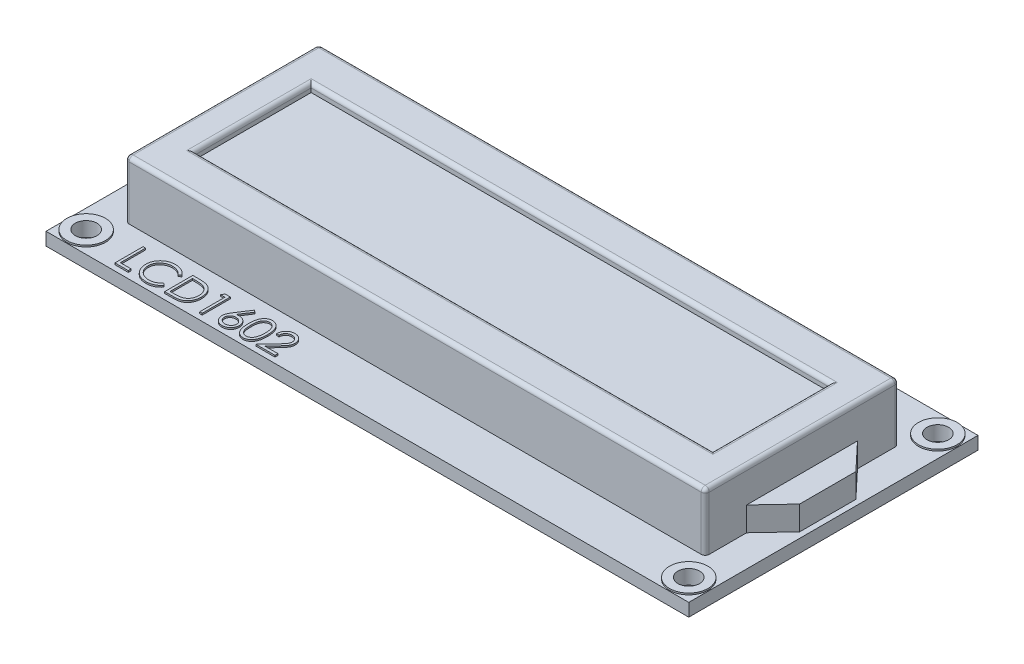
SolidWorks part; units mm, degrees
ref_plane "Front Plane" through (0, 0, 0) normal (0, 0, 1) x (1, 0, 0)
ref_plane "Top Plane" through (0, 0, 0) normal (0, 1, 0) x (1, 0, 0)
ref_plane "Right Plane" through (0, 0, 0) normal (1, 0, 0) x (0, 0, -1)
sketch "Sketch1" plane through (0, 0, 0) normal (0, 1, 0) x (1, 0, 0)
  line L0 (-31.9, 15.9) -> (6.2, 15.9) construction
  line L1 (40, 18) -> (-40, 18)
  line L2 (40, 18) -> (40, -18)
  line L3 (40, -18) -> (-40, -18)
  line L4 (-40, 18) -> (-40, -18)
  line L5 (0, -18) -> (0, 18) construction
  line L6 (40, 0) -> (-40, 0) construction
  line L7 (37.5, -15.5) -> (-37.5, -15.5) construction
  line L8 (37.5, -15.5) -> (37.5, 15.5) construction
  line L9 (37.5, 15.5) -> (-37.5, 15.5) construction
  line L10 (-37.5, -15.5) -> (-37.5, 15.5) construction
  line L11 (0, 15.5) -> (0, -15.5) construction
  line L12 (37.5, 0) -> (-37.5, 0) construction
  circle A0 centre (-37.5, 15.5) radius 1.35
  circle A1 centre (37.5, 15.5) radius 1.35
  circle A2 centre (37.5, -15.5) radius 1.35
  circle A3 centre (-37.5, -15.5) radius 1.35
  circle A4 centre (-31.9, 15.9) radius 0.5
  circle A5 centre (-29.36, 15.9) radius 0.5
  circle A6 centre (-26.82, 15.9) radius 0.5
  circle A7 centre (-24.28, 15.9) radius 0.5
  circle A8 centre (-21.74, 15.9) radius 0.5
  circle A9 centre (-19.2, 15.9) radius 0.5
  circle A10 centre (-16.66, 15.9) radius 0.5
  circle A11 centre (-14.12, 15.9) radius 0.5
  circle A12 centre (-11.58, 15.9) radius 0.5
  circle A13 centre (-9.04, 15.9) radius 0.5
  circle A14 centre (-6.5, 15.9) radius 0.5
  circle A15 centre (-3.96, 15.9) radius 0.5
  circle A16 centre (-1.42, 15.9) radius 0.5
  circle A17 centre (1.12, 15.9) radius 0.5
  circle A18 centre (3.66, 15.9) radius 0.5
  circle A19 centre (6.2, 15.9) radius 0.5
  point P0 (0, 0)
  point P4 (0, 0)
  dimension "D5" = 2
  dimension "D10" = 1
  dimension "D11" = 16
  dimension "D1" = 80
  dimension "D2" = 36
  dimension "D3" = 31
  dimension "D4" = 75
  dimension "D7" = 8.1
  dimension "D8" = 2.1
  dimension "D9" = 38.1
  dimension "D6" = 2
extrude "Boss-Extrude1" add sketch "Sketch1" along normal blind 1.6
sketch "Sketch2" plane through (0, 1.6, 0) normal (0, 1, 0) x (1, 0, 0)
  line L1 (36.1, 12.05) -> (-36.1, 12.05)
  line L2 (36.1, 12.05) -> (36.1, -12.05)
  line L3 (36.1, -12.05) -> (-36.1, -12.05)
  line L4 (-36.1, 12.05) -> (-36.1, -12.05)
  line L5 (0, -12.05) -> (0, 12.05) construction
  line L6 (36.1, 0) -> (-36.1, 0) construction
  point P0 (0, 0)
  dimension "D1" = 24.1
  dimension "D2" = 72.2
extrude "Boss-Extrude2" add sketch "Sketch2" along normal blind 7.2
sketch "Sketch3" plane through (0, 8.8, 0) normal (0, 1, 0) x (1, 0, 0)
  line L1 (32.25, 7.25) -> (-32.25, 7.25)
  line L2 (32.25, 7.25) -> (32.25, -7.25)
  line L3 (32.25, -7.25) -> (-32.25, -7.25)
  line L4 (-32.25, 7.25) -> (-32.25, -7.25)
  line L5 (0, -7.25) -> (0, 7.25) construction
  line L6 (32.25, 0) -> (-32.25, 0) construction
  point P0 (0, 0)
  dimension "D1" = 64.5
  dimension "D2" = 14.5
extrude "Cut-Extrude1" cut sketch "Sketch3" against normal blind 1
sketch "Sketch4" plane through (0, 1.6, 0) normal (0, 1, 0) x (1, 0, 0)
  line L0 (0, 0) -> (40, 0) construction
  line L1 (40, -18) -> (40, 18) construction
  line L2 (36.1, -6.9) -> (36.1, 6.9)
  line L3 (36.1, -12.05) -> (36.1, 12.05) construction
  line L4 (36.1, -12.05) -> (36.1, 12.05) construction
  line L5 (36.1, 6.9) -> (39.3, 3.5)
  line L6 (39.3, 3.5) -> (39.3, -3.5)
  line L7 (36.1, -6.9) -> (39.3, -3.5)
  point P14 (39.3, 0)
  point P15 (36.1, 0)
  dimension "D1" = 3.2
  dimension "D2" = 13.8
  dimension "D3" = 7
extrude "Boss-Extrude3" add sketch "Sketch4" along normal blind 3
sketch "Sketch5" plane through (0, 0, 0) normal (0, -1, 0) x (1, 0, 0)
  line L0 (32.5, 11.5) -> (29.5, 11.5)
  line L1 (32.5, -11.5) -> (-32.5, -11.5) construction
  line L2 (32.5, -11.5) -> (32.5, 11.5) construction
  line L3 (32.5, 11.5) -> (-32.5, 11.5) construction
  line L4 (-32.5, -11.5) -> (-32.5, 11.5) construction
  line L5 (0, 11.5) -> (0, -11.5) construction
  line L6 (32.5, 0) -> (-32.5, 0) construction
  line L7 (29.5, 11.5) -> (26.5, 7.8157)
  line L8 (26.5, 7.8157) -> (26.8877, 7.5)
  line L9 (26.8877, 7.5) -> (29.7377, 11)
  line L10 (29.7377, 11) -> (32.5, 11)
  line L11 (32.5, 11) -> (32.5, 11.5)
  line L12 (-2.6123, 7.5) -> (0.2377, 11)
  line L13 (-3, 7.8157) -> (-2.6123, 7.5)
  line L14 (0, 11.5) -> (-3, 7.8157)
  line L15 (3, 11.5) -> (0, 11.5)
  line L16 (0.2377, 11) -> (3, 11)
  line L17 (3, 11) -> (3, 11.5)
  line L18 (-32.1123, 7.5) -> (-29.2623, 11)
  line L19 (-32.5, 7.8157) -> (-32.1123, 7.5)
  line L20 (-29.5, 11.5) -> (-32.5, 7.8157)
  line L21 (-26.5, 11.5) -> (-29.5, 11.5)
  line L22 (-29.2623, 11) -> (-26.5, 11)
  line L23 (-26.5, 11) -> (-26.5, 11.5)
  line L42 (-29.5, -11.5) -> (-26.5, -7.8157)
  line L43 (-26.5, -7.8157) -> (-26.8877, -7.5)
  line L44 (-26.8877, -7.5) -> (-29.7377, -11)
  line L45 (2.6123, -7.5) -> (-0.2377, -11)
  line L46 (3, -7.8157) -> (2.6123, -7.5)
  line L47 (0, -11.5) -> (3, -7.8157)
  line L48 (-3, -11.5) -> (0, -11.5)
  line L49 (-0.2377, -11) -> (-3, -11)
  line L50 (-3, -11) -> (-3, -11.5)
  line L51 (26.5, -11.5) -> (29.5, -11.5)
  line L52 (29.2623, -11) -> (26.5, -11)
  line L53 (26.5, -11) -> (26.5, -11.5)
  line L54 (29.5, -11.5) -> (32.5, -7.8157)
  line L55 (32.1123, -7.5) -> (29.2623, -11)
  line L56 (32.5, -7.8157) -> (32.1123, -7.5)
  line L57 (-32.5, -11.5) -> (-29.5, -11.5)
  line L58 (-29.7377, -11) -> (-32.5, -11)
  line L59 (-32.5, -11) -> (-32.5, -11.5)
  point P0 (0, 0)
  dimension "D1" = 23
  dimension "D2" = 65
  dimension "D3" = 0.5
  dimension "D4" = 0.5
  dimension "D5" = 6
  dimension "D6" = 3
  dimension "D7" = 4
  dimension "D8" = 3
extrude "Boss-Extrude4" add sketch "Sketch5" along normal blind 3
sketch "Sketch6" plane through (0, 1.6, 0) normal (0, 1, 0) x (1, 0, 0)
  line L0 (-32.9, 15.9) -> (-32.9, 17.9)
  line L1 (-32.9, 17.9) -> (-30.9, 17.9)
  line L2 (-30.9, 17.9) -> (-30.9, 15.9)
  line L3 (-30.36, 15.9) -> (-30.36, 17.9)
  line L4 (-30.36, 17.9) -> (-28.36, 17.9)
  line L5 (-28.36, 17.9) -> (-28.36, 15.9)
  line L6 (-27.82, 15.9) -> (-27.82, 17.9)
  line L7 (-27.82, 17.9) -> (-25.82, 17.9)
  line L8 (-25.82, 17.9) -> (-25.82, 15.9)
  line L9 (-25.28, 15.9) -> (-25.28, 17.9)
  line L10 (-25.28, 17.9) -> (-23.28, 17.9)
  line L11 (-23.28, 17.9) -> (-23.28, 15.9)
  line L12 (-22.74, 15.9) -> (-22.74, 17.9)
  line L13 (-22.74, 17.9) -> (-20.74, 17.9)
  line L14 (-20.74, 17.9) -> (-20.74, 15.9)
  line L15 (-20.2, 15.9) -> (-20.2, 17.9)
  line L16 (-20.2, 17.9) -> (-18.2, 17.9)
  line L17 (-18.2, 17.9) -> (-18.2, 15.9)
  line L18 (-17.66, 15.9) -> (-17.66, 17.9)
  line L19 (-17.66, 17.9) -> (-15.66, 17.9)
  line L20 (-15.66, 17.9) -> (-15.66, 15.9)
  line L21 (-15.12, 15.9) -> (-15.12, 17.9)
  line L22 (-15.12, 17.9) -> (-13.12, 17.9)
  line L23 (-13.12, 17.9) -> (-13.12, 15.9)
  line L24 (-12.58, 15.9) -> (-12.58, 17.9)
  line L25 (-12.58, 17.9) -> (-10.58, 17.9)
  line L26 (-10.58, 17.9) -> (-10.58, 15.9)
  line L27 (-10.04, 15.9) -> (-10.04, 17.9)
  line L28 (-10.04, 17.9) -> (-8.04, 17.9)
  line L29 (-8.04, 17.9) -> (-8.04, 15.9)
  line L30 (-7.5, 15.9) -> (-7.5, 17.9)
  line L31 (-7.5, 17.9) -> (-5.5, 17.9)
  line L32 (-5.5, 17.9) -> (-5.5, 15.9)
  line L33 (-4.96, 15.9) -> (-4.96, 17.9)
  line L34 (-4.96, 17.9) -> (-2.96, 17.9)
  line L35 (-2.96, 17.9) -> (-2.96, 15.9)
  line L36 (-2.42, 15.9) -> (-2.42, 17.9)
  line L37 (-2.42, 17.9) -> (-0.42, 17.9)
  line L38 (-0.42, 17.9) -> (-0.42, 15.9)
  line L39 (0.12, 15.9) -> (0.12, 17.9)
  line L40 (0.12, 17.9) -> (2.12, 17.9)
  line L41 (2.12, 17.9) -> (2.12, 15.9)
  line L42 (2.66, 15.9) -> (2.66, 17.9)
  line L43 (2.66, 17.9) -> (4.66, 17.9)
  line L44 (4.66, 17.9) -> (4.66, 15.9)
  line L45 (5.2, 15.9) -> (5.2, 17.9)
  line L46 (5.2, 17.9) -> (7.2, 17.9)
  line L47 (7.2, 17.9) -> (7.2, 15.9)
  line L48 (-31.1242, 12.1713) -> (-31.1242, 14.5942) construction
  line L49 (-32.5503, -17.3154) -> (-14.12, -17.3154) construction
  arc A0 (-32.9, 15.9) -> (-30.9, 15.9) centre (-31.9, 15.9) ccw
  arc A1 (-30.36, 15.9) -> (-28.36, 15.9) centre (-29.36, 15.9) ccw
  arc A2 (-27.82, 15.9) -> (-25.82, 15.9) centre (-26.82, 15.9) ccw
  arc A3 (-25.28, 15.9) -> (-23.28, 15.9) centre (-24.28, 15.9) ccw
  arc A4 (-22.74, 15.9) -> (-20.74, 15.9) centre (-21.74, 15.9) ccw
  arc A5 (-20.2, 15.9) -> (-18.2, 15.9) centre (-19.2, 15.9) ccw
  arc A6 (-17.66, 15.9) -> (-15.66, 15.9) centre (-16.66, 15.9) ccw
  arc A7 (-15.12, 15.9) -> (-13.12, 15.9) centre (-14.12, 15.9) ccw
  arc A8 (-12.58, 15.9) -> (-10.58, 15.9) centre (-11.58, 15.9) ccw
  arc A9 (-10.04, 15.9) -> (-8.04, 15.9) centre (-9.04, 15.9) ccw
  arc A10 (-7.5, 15.9) -> (-5.5, 15.9) centre (-6.5, 15.9) ccw
  arc A11 (-4.96, 15.9) -> (-2.96, 15.9) centre (-3.96, 15.9) ccw
  arc A12 (-2.42, 15.9) -> (-0.42, 15.9) centre (-1.42, 15.9) ccw
  arc A13 (0.12, 15.9) -> (2.12, 15.9) centre (1.12, 15.9) ccw
  arc A14 (2.66, 15.9) -> (4.66, 15.9) centre (3.66, 15.9) ccw
  arc A15 (5.2, 15.9) -> (7.2, 15.9) centre (6.2, 15.9) ccw
  circle A16 centre (-37.5, 15.5) radius 1.35
  circle A17 centre (-37.5, 15.5) radius 2.4
  circle A18 centre (37.5, 15.5) radius 1.35
  circle A19 centre (37.5, 15.5) radius 2.4
  circle A20 centre (37.5, -15.5) radius 1.35
  circle A21 centre (37.5, -15.5) radius 2.4
  circle A22 centre (-37.5, -15.5) radius 1.35
  circle A23 centre (-37.5, -15.5) radius 2.4
  circle A24 centre (-31.9, 15.9) radius 0.5
  circle A25 centre (-29.36, 15.9) radius 0.5
  circle A26 centre (-26.82, 15.9) radius 0.5
  circle A27 centre (-24.28, 15.9) radius 0.5
  circle A28 centre (-21.74, 15.9) radius 0.5
  circle A29 centre (-19.2, 15.9) radius 0.5
  circle A30 centre (-16.66, 15.9) radius 0.5
  circle A31 centre (-14.12, 15.9) radius 0.5
  circle A32 centre (-11.58, 15.9) radius 0.5
  circle A33 centre (-9.04, 15.9) radius 0.5
  circle A34 centre (-6.5, 15.9) radius 0.5
  circle A35 centre (-3.96, 15.9) radius 0.5
  circle A36 centre (-1.42, 15.9) radius 0.5
  circle A37 centre (1.12, 15.9) radius 0.5
  circle A38 centre (3.66, 15.9) radius 0.5
  circle A39 centre (6.2, 15.9) radius 0.5
  text T0 "Gnd\r\nVdd\r\nV0\r\nRS\r\nRW\r\nE\r\nD0\r\nD1\r\nD2\r\nD3\r\nD4\r\nD5\r\nD6\r\nD7\r\nBLA\r\nBLK" font "Century Gothic" height 0.9
  text T1 "LCD1602"
  dimension "D1" = 2
  dimension "D4" = 4.8
  dimension "D2" = 2
  dimension "D5" = 2
  dimension "D7" = 16
  dimension "D3" = 16
  dimension "D6" = 2
extrude "Boss-Extrude5" add sketch "Sketch6" along normal blind 0.2
fillet "Fillet1" radius 0.5 12 edges at (0, 8.8, -12.05) (36.1, 8.8, 0) (0, 8.8, 12.05) (-36.1, 8.8, 0) (32.25, 8.8, 0) (0, 8.8, -7.25) (-32.25, 8.8, 0) (0, 8.8, 7.25) (-36.1, 5.2, -12.05) (36.1, 5.2, -12.05) (36.1, 5.2, 12.05) (-36.1, 5.2, 12.05)
